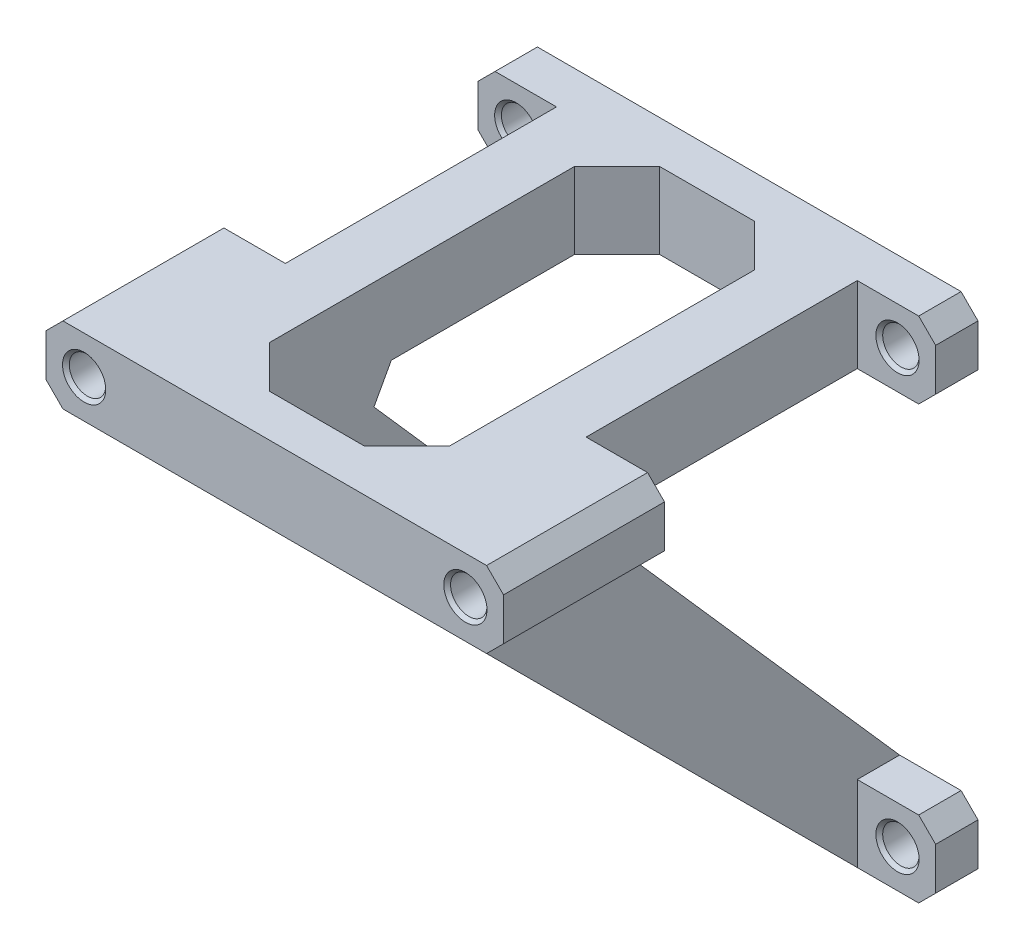
SolidWorks part; units mm, degrees
ref_plane "Front" through (0, 0, 0) normal (0, 0, 1) x (1, 0, 0)
ref_plane "Top" through (0, 0, 0) normal (0, 1, 0) x (1, 0, 0)
ref_plane "Right" through (0, 0, 0) normal (1, 0, 0) x (0, 0, -1)
sketch "Sketch1" plane through (0, 0, 0) normal (0, 0, 1) x (1, 0, 0)
  line L1 (0, 0) -> (54, 0)
  line L2 (0, 0) -> (0, 60)
  line L3 (0, 60) -> (54, 60)
  line L4 (54, 0) -> (54, 60)
  dimension "D1" = 54
  dimension "D2" = 60
extrude "Boss-Extrude1" add sketch "Sketch1" along normal blind 5
sketch "Sketch5" plane through (0, 0, 0) normal (-1, 0, 0) x (0, 0, 1)
  line L1 (56, 60) -> (5, 60)
  line L2 (5, 60) -> (5, 0)
  line L3 (5, 0) -> (56, 51)
  line L4 (56, 51) -> (56, 60)
  dimension "D1" = 45
  dimension "D2" = 9
extrude "Boss-Extrude2" add sketch "Sketch5" against normal up to surface (54 mm away) up to face at (54, 30, 2.5)
sketch "Sketch2" plane through (0, 0, 0) normal (0, 0, 1) x (1, 0, 0)
  line L1 (4.5, 55.5) -> (49.5, 55.5)
  line L2 (4.5, 55.5) -> (4.5, 4.5)
  line L3 (4.5, 4.5) -> (49.5, 4.5)
  line L4 (49.5, 55.5) -> (49.5, 4.5)
  line L6 (0, 60) -> (0, 0) construction
  line L7 (54, 60) -> (0, 60) construction
  dimension "D1" = 45
  dimension "D2" = 51
  dimension "D3" = 4.5
  dimension "D4" = 4.5
sketch "Sketch6" plane through (0, 60, 0) normal (0, 1, 0) x (1, 0, 0)
  line L0 (0, -56) -> (0, 0) construction
  line L1 (0, -5) -> (9.25, -5)
  line L2 (0, -5) -> (0, -37)
  line L3 (0, -37) -> (9.25, -37)
  line L4 (9.25, -5) -> (9.25, -37)
  line L5 (54, 0) -> (0, 0) construction
  dimension "D1" = 32
  dimension "D2" = 5
  dimension "D3" = 9.25
extrude "Cut-Extrude1" cut sketch "Sketch6" against normal through all
sketch "Sketch8" plane through (0, 0, 0) normal (0, 0, -1) x (-1, 0, 0)
  line L0 (0, 60) -> (0, 0) construction
  line L1 (0, 51) -> (-9.25, 51)
  line L2 (0, 51) -> (0, 9)
  line L3 (0, 9) -> (-9.25, 9)
  line L4 (-9.25, 51) -> (-9.25, 9)
  line L5 (-54, 60) -> (0, 60) construction
  line L6 (0, 0) -> (-54, 0) construction
  dimension "D1" = 9.25
  dimension "D2" = 9
  dimension "D3" = 9
extrude "Cut-Extrude3" cut sketch "Sketch8" against normal through all
ref_plane "Plane1" through (27, 0, 0) normal (1, 0, 0) x (0, 0, -1)
mirror "Mirror1" about plane through (27, 0, 0) normal (1, 0, 0) of "Cut-Extrude3", "Cut-Extrude1"
hole_wizard "M4 Clearance Hole2" positions "Sketch9" profile "Sketch10" hole size "M4" standard "DIN" end condition through all
sketch "Sketch9" plane through (0, 0, 0) normal (0, 0, -1) x (-1, 0, 0)
  point P0 (-4.5, 55.5)
  point P3 (-49.5, 55.5)
  point P6 (-49.5, 4.5)
  point P9 (-4.5, 4.5)
sketch "Sketch10" plane through (4.5, 55.5, 0) normal (1, 0, 0) x (0, 1, 0)
  line L0 (0, 0) -> (0, 56)
  line L1 (0, 56) -> (2.15, 56)
  line L2 (2.15, 56) -> (2.15, 0)
  line L5 (2.15, 0) -> (0, 0)
  line L11 (0, -6.35) -> (0, 107.95) construction
  dimension "Thru Hole Dia." = 4.3
  dimension "Thru Hole Depth" = 56
sketch "Sketch11" plane through (9.25, 0, 0) normal (-1, 0, 0) x (0, 0, 1)
  line L0 (0, 9) -> (37, 51)
  line L1 (37, 51) -> (0, 51)
  line L2 (0, 51) -> (0, 9)
extrude "Cut-Extrude4" cut sketch "Sketch11" against normal through all
sketch "Sketch12" plane through (0, 60, 0) normal (0, 1, 0) x (1, 0, 0)
  line L0 (54, 0) -> (0, 0) construction
  line L1 (16.4, -5) -> (37.6, -5)
  line L2 (16.4, -5) -> (16.4, -51)
  line L3 (16.4, -51) -> (37.6, -51)
  line L4 (37.6, -5) -> (37.6, -51)
  line L5 (9.25, -37) -> (9.25, -5) construction
  line L6 (44.75, -37) -> (44.75, -5) construction
  line L7 (54, -56) -> (0, -56) construction
  dimension "D1" = 5
  dimension "D2" = 7.15
  dimension "D3" = 7.15
  dimension "D4" = 5
extrude "Cut-Extrude5" cut sketch "Sketch12" against normal through all
chamfer "Chamfer1" distance 2 angle 45 12 edges at (0, 60, 2.5) (0, 9, 2.5) (0, 51, 2.5) (0, 51, 46.5) (54, 60, 2.5) (0, 60, 46.5) (54, 60, 46.5) (54, 0, 2.5) (0, 0, 2.5) (54, 51, 46.5) (54, 9, 2.5) (54, 51, 2.5)
chamfer "Chamfer2" distance 5 angle 70 2 edges at (41.175, 51, 37) (12.825, 51, 37)
sketch "Sketch13" plane through (0, 0, 0) normal (0, 0, -1) x (-1, 0, 0)
  line L1 (-37.6, 46) -> (-16.4, 46)
  line L2 (-37.6, 46) -> (-37.6, 51)
  line L3 (-37.6, 51) -> (-16.4, 51)
  line L4 (-16.4, 46) -> (-16.4, 51)
extrude "Cut-Extrude6" cut sketch "Sketch13" against normal through all
chamfer "Chamfer3" distance 5 angle 45 6 edges at (16.4, 55.5, 51) (37.6, 55.5, 51) (16.4, 55.5, 5) (37.6, 55.5, 5) (37.6, 7.3378, 5) (16.4, 7.3378, 5)
sketch "Sketch14" plane through (0, 0, 37) normal (0, 0, -1) x (-1, 0, 0)
  line L0 (-2, 51) -> (-9.25, 43.75)
  line L2 (-9.25, 43.75) -> (-9.25, 51)
  line L3 (-9.25, 51) -> (-2, 51)
  line L4 (-9.25, 0) -> (-9.25, 51) construction
  dimension "D1" = 45
extrude "Boss-Extrude3" add sketch "Sketch14" against normal up to surface (19 mm away) up to face at (27, 54, 56)
mirror "Mirror3" about plane through (27, 0, 0) normal (1, 0, 0) of "Boss-Extrude3"
sketch "Sketch15" plane through (9.25, 0, 0) normal (1, 0, 0) x (0, 0, -1)
  line L0 (-48.75, 43.75) -> (-56, 51)
  line L1 (-56, 51) -> (-56, 43.75)
  line L2 (-56, 43.75) -> (-48.75, 43.75)
extrude "Cut-Extrude7" cut sketch "Sketch15" against normal through all and the other way through all
chamfer "Chamfer4" distance 0.4 angle 45 4 edges at (47.35, 55.5, 56) (47.35, 55.5, 37) (6.65, 55.5, 37) (2.35, 55.5, 56)
chamfer "Chamfer5" distance 0.4 angle 45 8 edges at (2.35, 4.5, 5) (2.35, 4.5, 0) (47.35, 4.5, 0) (51.65, 4.5, 5) (47.35, 55.5, 0) (51.65, 55.5, 5) (2.35, 55.5, 5) (2.35, 55.5, 0)
